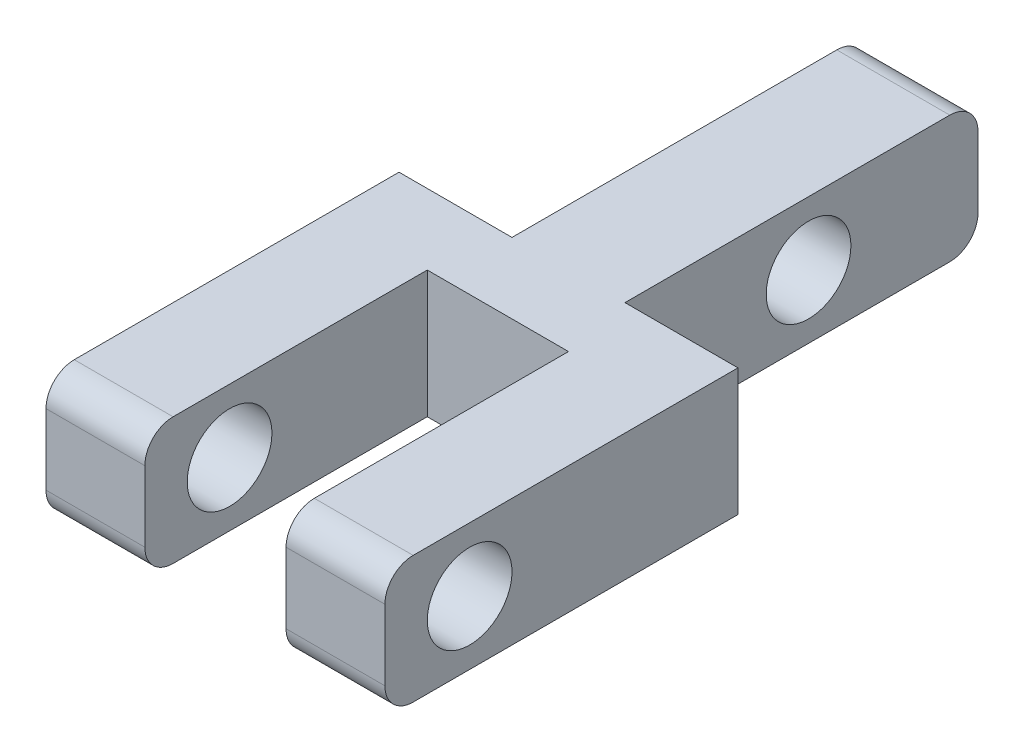
SolidWorks part; units mm, degrees
ref_plane "Alzado" through (0, 0, 0) normal (0, 0, 1) x (1, 0, 0)
ref_plane "Planta" through (0, 0, 0) normal (0, 1, 0) x (1, 0, 0)
ref_plane "Vista lateral" through (0, 0, 0) normal (1, 0, 0) x (0, 0, -1)
sketch "Croquis1" plane through (0, 0, 0) normal (1, 0, 0) x (0, 0, -1)
  line L0 (-11.5, 2.25) -> (11.5, 2.25)
  line L2 (-12.5, 0) -> (12.5, 0) construction
  line L3 (-12.5, 1.25) -> (-12.5, -1.25)
  line L4 (-11.5, -2.25) -> (11.5, -2.25)
  line L5 (12.5, 1.25) -> (12.5, -1.25)
  arc A0 (-12.5, -1.25) -> (-11.5, -2.25) centre (-11.5, -1.25) ccw
  arc A1 (-12.5, 1.25) -> (-11.5, 2.25) centre (-11.5, 1.25) cw
  arc A2 (11.5, -2.25) -> (12.5, -1.25) centre (11.5, -1.25) ccw
  arc A3 (11.5, 2.25) -> (12.5, 1.25) centre (11.5, 1.25) cw
  point P1 (0, 0)
  point P9 (-12.5, -2.25)
  point P13 (-12.5, 2.25)
  point P16 (12.5, -2.25)
  point P19 (12.5, 2.25)
  dimension "D3" = 1
  dimension "D4" = 1
  dimension "D1" = 2.25
  dimension "D2" = 25
extrude "Saliente-Extruir1" add sketch "Croquis1" along normal mid plane 4
sketch "Croquis2" plane through (0, 0, 0) normal (1, 0, 0) x (0, 0, -1)
  line L0 (-12.5, 1.25) -> (-12.5, -1.25) construction
  line L1 (12.5, -1.25) -> (12.5, 1.25) construction
  circle A0 centre (-9.5, 0) radius 1.5
  circle A1 centre (6.5, 0) radius 1.5
  dimension "D1" = 3
  dimension "D3" = 3
  dimension "D2" = 3
  dimension "D4" = 6
extrude "Cortar-Extruir1" cut sketch "Croquis2" against normal through all both and the other way through all
sketch "Croquis3" plane through (0, 0, 0) normal (1, 0, 0) x (0, 0, -1)
  line L0 (-12.5, 1.25) -> (-12.5, -1.25) construction
  line L1 (-12.5, 1.25) -> (-12.5, -1.25)
  line L2 (-11.5, 2.25) -> (0, 2.25)
  line L3 (11.5, 2.25) -> (-11.5, 2.25) construction
  line L4 (0, 2.25) -> (0, -2.25)
  line L5 (-11.5, -2.25) -> (11.5, -2.25) construction
  line L6 (0, -2.25) -> (-11.5, -2.25)
  circle A0 centre (-9.5, 0) radius 1.5 construction
  circle A1 centre (-9.5, 0) radius 1.5
  arc A2 (-11.5, 2.25) -> (-12.5, 1.25) centre (-11.5, 1.25) ccw construction
  arc A3 (-11.5, 2.25) -> (-12.5, 1.25) centre (-11.5, 1.25) ccw
  arc A4 (-12.5, -1.25) -> (-11.5, -2.25) centre (-11.5, -1.25) ccw construction
  arc A5 (-12.5, -1.25) -> (-11.5, -2.25) centre (-11.5, -1.25) ccw
extrude "Saliente-Extruir2" add sketch "Croquis3" along normal mid plane 12
sketch "Croquis4" plane through (0, 0, 0) normal (1, 0, 0) x (0, 0, -1)
  line L0 (-11.5, 2.25) -> (-2.5, 2.25)
  line L1 (0, 2.25) -> (-11.5, 2.25) construction
  line L2 (-2.5, 2.25) -> (-2.5, -2.25)
  line L3 (-11.5, -2.25) -> (0, -2.25) construction
  line L4 (-12.5, 1.25) -> (-12.5, -1.25)
  line L5 (-11.5, -2.25) -> (0, -2.25)
  line L6 (0, -2.25) -> (0, 2.25)
  line L7 (0, 2.25) -> (-11.5, 2.25)
  line L8 (-12.5, 1.25) -> (-12.5, -1.25)
  line L12 (-2.5, -2.25) -> (-11.5, -2.25)
  arc A2 (-11.5, 2.25) -> (-12.5, 1.25) centre (-11.5, 1.25) ccw
  arc A3 (-12.5, -1.25) -> (-11.5, -2.25) centre (-11.5, -1.25) ccw
  arc A4 (-11.5, 2.25) -> (-12.5, 1.25) centre (-11.5, 1.25) ccw
  arc A5 (-12.5, -1.25) -> (-11.5, -2.25) centre (-11.5, -1.25) ccw
  dimension "D2" = 10
  dimension "D1" = 0
extrude "Cortar-Extruir2" cut sketch "Croquis4" against normal mid plane 5
